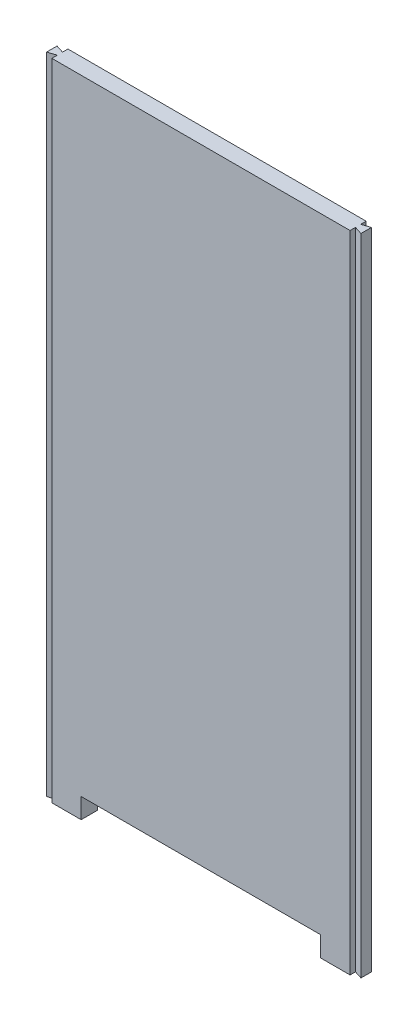
SolidWorks part; units mm, degrees
ref_plane "Front Plane" through (0, 0, 0) normal (0, 0, 1) x (1, 0, 0)
ref_plane "Top Plane" through (0, 0, 0) normal (0, 1, 0) x (1, 0, 0)
ref_plane "Right Plane" through (0, 0, 0) normal (1, 0, 0) x (0, 0, -1)
sketch "Sketch1" plane through (0, 0, 0) normal (0, 0, 1) x (1, 0, 0)
  line L1 (0, 0) -> (37, 0)
  line L2 (0, 0) -> (0, 80)
  line L3 (0, 80) -> (37, 80)
  line L4 (37, 0) -> (37, 80)
  dimension "D1" = 80
  dimension "D2" = 37
extrude "Boss-Extrude1" add sketch "Sketch1" along normal blind 2
sketch "Sketch2" plane through (0, 80, 0) normal (0, 1, 0) x (1, 0, 0)
  line L0 (37, -1) -> (38, -1) construction
  line L1 (37, -2) -> (37, 0) construction
  line L2 (38, -1.65) -> (38, -0.35)
  line L3 (37, -1) -> (37, -0.35) construction
  line L4 (37, -0.675) -> (38, -0.35)
  line L5 (37, -1) -> (37, -1.65) construction
  line L6 (37, -1.325) -> (38, -1.65)
  line L7 (37, -0.675) -> (37, -1)
  line L8 (37, -0.675) -> (37, -1.325)
  line L9 (18.5, 0) -> (18.5, -2) construction
  line L10 (37, 0) -> (0, 0) construction
  line L11 (37, -2) -> (0, -2) construction
  line L12 (0, -0.675) -> (-1, -0.35)
  line L13 (-1, -1.65) -> (-1, -0.35)
  line L14 (0, -1.325) -> (-1, -1.65)
  line L15 (0, -0.675) -> (0, -1.325)
  line M5 (37, -2) -> (37, 0)
  dimension "D1" = 1
  dimension "D2" = 0.65
extrude "Boss-Extrude2" add sketch "Sketch2" against normal up to surface (80 mm away) contours L6 L2 L4 M5 | L14 L13 L12 L15 region at (37.5556, 80, 1) up to face at (18.5, 0, 1)
sketch "Sketch3" plane through (0, 0, 2) normal (0, 0, 1) x (1, 0, 0)
  line L0 (0, 0) -> (18.5, 0) construction
  line L1 (0, 0) -> (37, 0) construction
  line L2 (18.5, 0) -> (18.5, 2.5) construction
  line L3 (3.6365, 2.5) -> (33.3635, 2.5)
  line L4 (33.3635, 2.5) -> (33.3635, 0)
  line L5 (3.6365, 2.5) -> (3.6365, 0)
  line L6 (3.6365, 0) -> (33.3635, 0)
  dimension "D1" = 2.5
extrude "Cut-Extrude1" cut sketch "Sketch3" against normal up to surface (2 mm away) contours L3 L4 L6 L5 up to face at (18.5, 40, 0)
